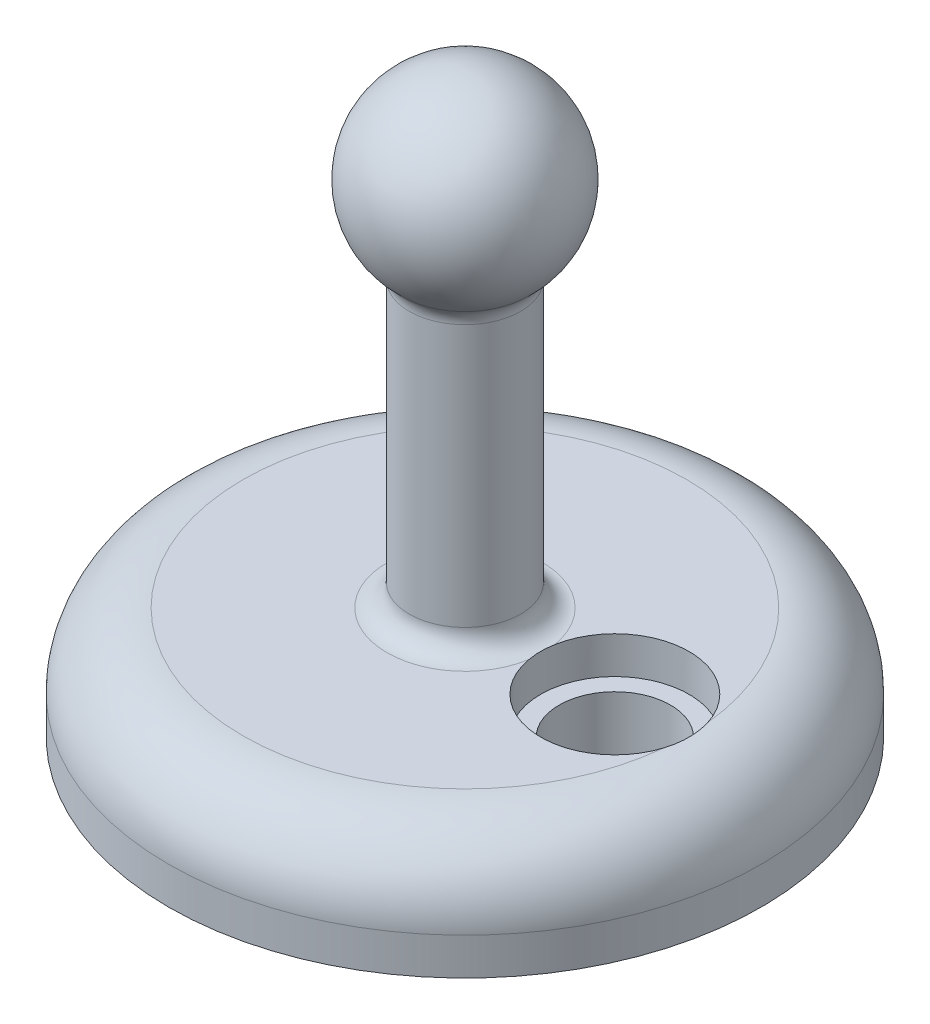
SolidWorks part; units mm, degrees
ref_plane "Front Plane" through (0, 0, 0) normal (0, 0, 1) x (1, 0, 0)
ref_plane "Top Plane" through (0, 0, 0) normal (0, 1, 0) x (1, 0, 0)
ref_plane "Right Plane" through (0, 0, 0) normal (1, 0, 0) x (0, 0, -1)
sketch "Sketch1" plane through (0, 0, 0) normal (0, 1, 0) x (1, 0, 0)
  line L0 (0, 34.9011) -> (0, 39.9011) construction
  circle A0 centre (0, 0) radius 39.9011
  circle A1 centre (0, 0) radius 34.9011 construction
  circle A2 centre (17.5, 28.3909) radius 1.55 construction
  point P8 (0, 0)
  dimension "D1" = 5
extrude "Boss-Extrude1" add sketch "Sketch1" along normal blind 15
fillet "Fillet1" radius 10 1 edges at (0, 15, 39.9011)
sketch "Sketch2" plane through (0, 0, 0) normal (0, -1, 0) x (1, 0, 0)
  circle A0 centre (-16.5, 28.5788) radius 1.75
  circle A1 centre (16.5, 28.5788) radius 1.75
  circle A2 centre (33, 0) radius 1.75
  circle A3 centre (16.5, -28.5788) radius 1.75
  circle A4 centre (-16.5, -28.5788) radius 1.75
  circle A5 centre (-33, 0) radius 1.75
  circle A12 centre (-16.5, -28.5788) radius 1.75 construction
  circle A13 centre (-33, 0) radius 1.75 construction
  circle A14 centre (-16.5, 28.5788) radius 1.75 construction
  circle A16 centre (33, 0) radius 1.75 construction
  circle A17 centre (16.5, -28.5788) radius 1.75 construction
  circle A18 centre (16.5, 28.5788) radius 1.75 construction
  dimension "D1" = 3.5
extrude "Cut-Extrude1" cut sketch "Sketch2" against normal offset from surface (10 mm away) 5 up to face at (0, 15, 29.9011)
fillet "Fillet2" radius 1 6 edges at (33, 10, 1.75) (16.5, 10, -26.8288) (-16.5, 10, -26.8288) (-33, 10, 1.75) (-16.5, 10, 30.3288) (16.5, 10, 30.3288)
sketch "Sketch3" plane through (0, 0, 0) normal (0, -1, 0) x (1, 0, 0)
  circle A0 centre (-16.5, 28.5788) radius 2.5
  circle A1 centre (-33, 0) radius 2.5
  circle A2 centre (-16.5, -28.5788) radius 2.5
  circle A3 centre (16.5, -28.5788) radius 2.5
  circle A4 centre (33, 0) radius 2.5
  circle A5 centre (16.5, 28.5788) radius 2.5
  circle A6 centre (16.5, 28.5788) radius 1.75 construction
  circle A7 centre (-16.5, 28.5788) radius 1.75 construction
  circle A8 centre (-33, 0) radius 1.75 construction
  circle A9 centre (-16.5, -28.5788) radius 1.75 construction
  circle A10 centre (16.5, -28.5788) radius 1.75 construction
  circle A11 centre (33, 0) radius 1.75 construction
  dimension "D1" = 5
extrude "Cut-Extrude2" cut sketch "Sketch3" against normal blind 6
sketch "Sketch4" plane through (0, 15, 0) normal (0, 1, 0) x (1, 0, 0)
  circle A0 centre (0, 0) radius 7.5
  circle A1 centre (0, 0) radius 29.9011 construction
  dimension "D1" = 15
extrude "Boss-Extrude2" add sketch "Sketch4" along normal blind 50
sketch "Sketch5" plane through (0, 0, 0) normal (0, 0, 1) x (1, 0, 0)
  line L0 (7.5, 65) -> (-7.5, 65) construction
  line L1 (0, 77.7) -> (0, 52.3)
  circle A0 centre (0, 65) radius 12.7 construction
  arc A1 (0, 77.7) -> (0, 52.3) centre (0, 65) cw
  dimension "D1" = 25.4
revolve "Revolve1" add sketch "Sketch5" angle 360 about L1
fillet "Fillet3" radius 3 2 edges at (0, 54.7511, 7.5) (0, 15, 7.5)
sketch "Sketch6" plane through (0, 15, 0) normal (0, 1, 0) x (1, 0, 0)
  line L0 (29.9011, 0) -> (10.5, 0) construction
  circle A0 centre (20.2005, 0) radius 7.5
  circle A2 centre (0, 0) radius 29.9011 construction
  circle A3 centre (0, 0) radius 10.5 construction
  point P4 (20.2005, 0)
  dimension "D1" = 15
extrude "Cut-Extrude4" cut sketch "Sketch6" against normal up to surface (15 mm away) and the other way blind 10 up to face at (-33, 0, -2.5)
sketch "Sketch7" plane through (0, 15, 0) normal (0, 1, 0) x (1, 0, 0)
  circle A0 centre (20.2005, 0) radius 10
  circle A1 centre (20.2005, 0) radius 7.5 construction
  dimension "D1" = 20
extrude "Cut-Extrude5" cut sketch "Sketch7" against normal blind 5 and the other way blind 5
sketch "Sketch8" plane through (0, 0, 0) normal (0, -1, 0) x (1, 0, 0)
  line L0 (9.0494, 16.6616) -> (-32.4714, 16.6616) construction
  text T0 "^UP\r\nphonemonut V2\r\nhitchco-mk4"
extrude "Cut-Extrude6" cut sketch "Sketch8" against normal blind 1
